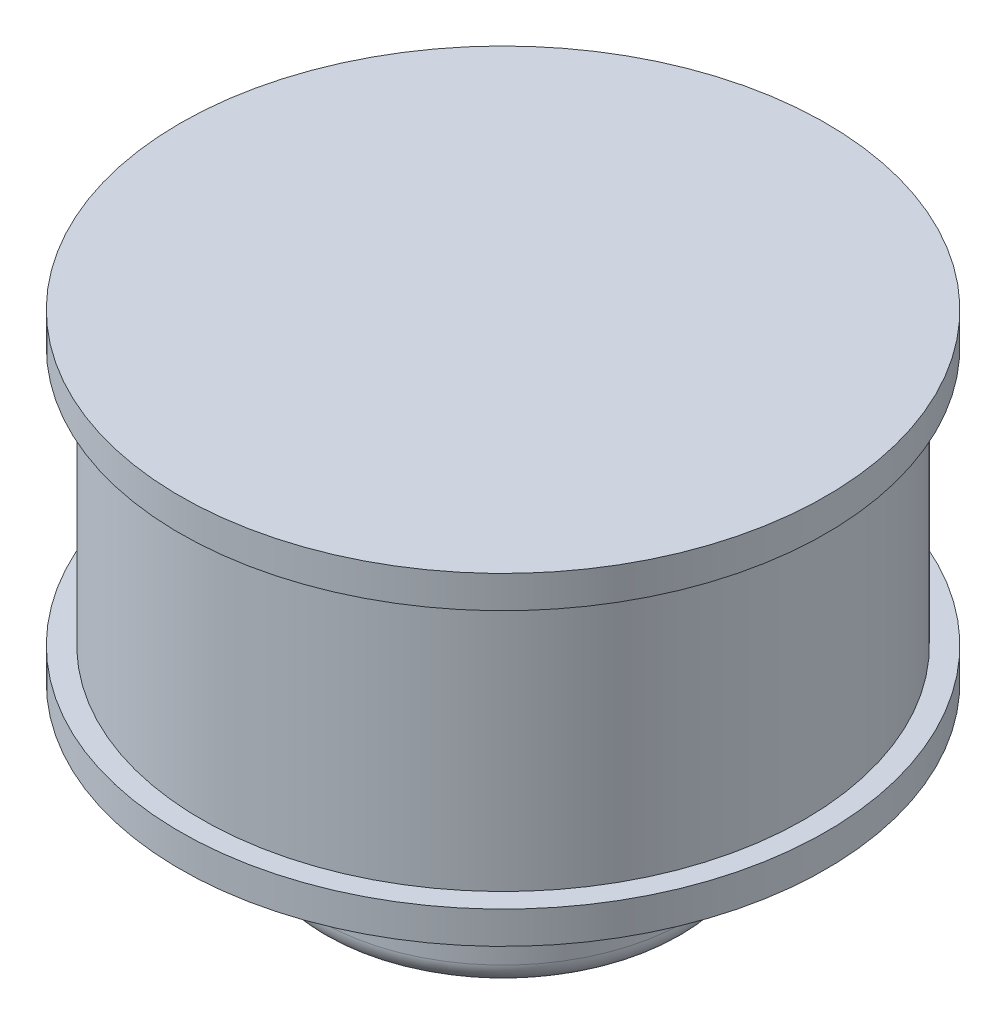
SolidWorks part; units mm, degrees
material "ABS"
ref_plane "Front Plane" through (0, 0, 0) normal (0, 0, 1) x (1, 0, 0)
ref_plane "Top Plane" through (0, 0, 0) normal (0, 1, 0) x (1, 0, 0)
ref_plane "Right Plane" through (0, 0, 0) normal (1, 0, 0) x (0, 0, -1)
sketch "Sketch1" plane through (0, 0, 0) normal (0, 0, 1) x (1, 0, 0)
  line L2 (-8.5, -6.35) -> (-8.5, 0)
  line L3 (-8.5, 0) -> (-15, 0)
  line L4 (-15, 0) -> (-15, 1.5)
  line L5 (-15, 1.5) -> (-14, 1.5)
  line L6 (-14, 1.5) -> (-14, 13.5)
  line L7 (-14, 13.5) -> (-15, 13.5)
  line L8 (-15, 13.5) -> (-15, 15)
  line L9 (-15, 15) -> (0, 15)
  line L10 (0, 15) -> (0, 7.65)
  line L11 (-4, -6.35) -> (-8.5, -6.35)
  line L12 (-4, 7.65) -> (-4, -6.35)
  line L13 (0, 7.65) -> (-4, 7.65)
  dimension "D1" = 8.5
  dimension "D2" = 1
  dimension "D3" = 6.35
  dimension "D4" = 1.5
  dimension "D5" = 4
  dimension "D6" = 14
  dimension "D7" = 15
  dimension "D8" = 14
revolve "Revolve1" add sketch "Sketch1" angle 360 about L10
fillet "Fillet1" radius 1 2 edges at (-8.5, -6.35, 0) (-4, -6.35, 0)
hole_wizard "M2x0.4 Tapped Hole1" positions "Sketch2" profile "Sketch3" tap size "M2x0.4" standard "ANSI Metric" end condition up to next
sketch "Sketch2" plane through (0, 0, 0) normal (0, 0, 1) x (1, 0, 0)
  line L0 (-7.5, -6.35) -> (7.5, -6.35) construction
  point P0 (0, -2.35)
  dimension "D1" = 4
sketch "Sketch3" plane through (0, -2.35, 0) normal (1, 0, 0) x (0, 1, 0)
  line L0 (0, 0) -> (0, 8.5)
  line L1 (0, 8.5) -> (0.8, 8.5)
  line L2 (0.8, 8.5) -> (0.8, 0)
  line L5 (0.8, 0) -> (0, 0)
  line L11 (0, -6.35) -> (0, 107.95) construction
  dimension "Thru Tap Drill Dia." = 1.6
  dimension "Thru Tap Drill Depth" = 8.5
cosmetic thread "Hole Thread1"
